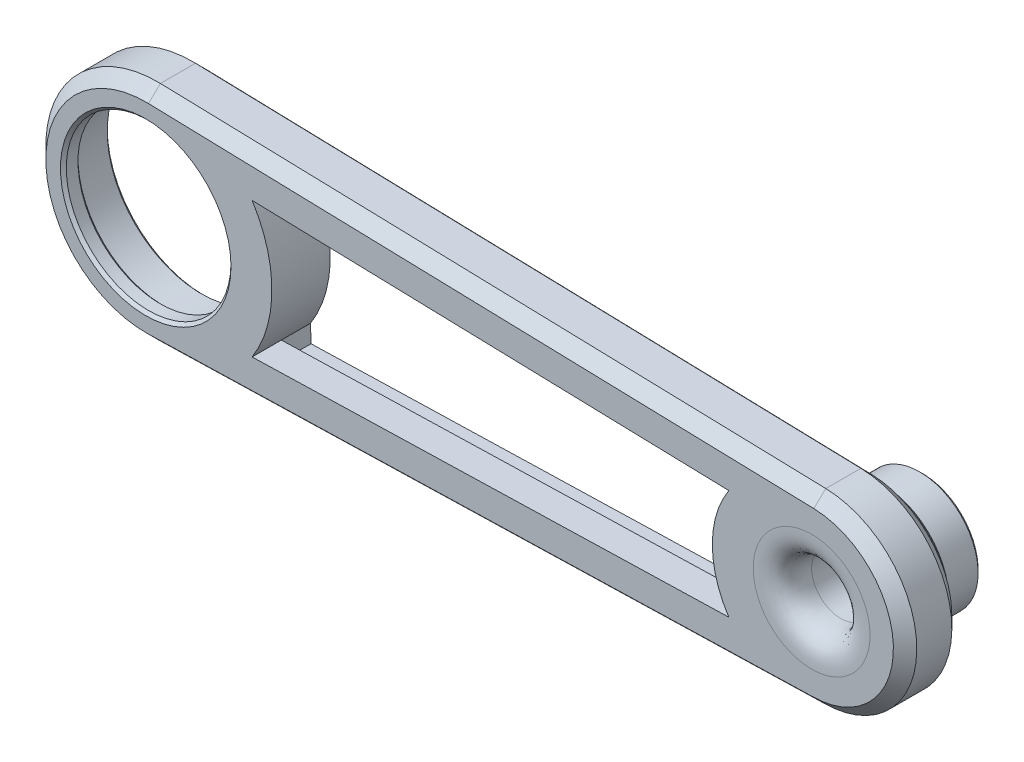
SolidWorks part; units mm, degrees
material "PEI"
ref_plane "前视基准面" through (0, 0, 0) normal (0, 0, 1) x (1, 0, 0)
ref_plane "上视基准面" through (0, 0, 0) normal (0, 1, 0) x (1, 0, 0)
ref_plane "右视基准面" through (0, 0, 0) normal (1, 0, 0) x (0, 0, -1)
other "Configuration Table"
sketch "草图1" plane through (0, 0, 0) normal (0, 0, 1) x (1, 0, 0)
  line L0 (0, 0) -> (114, 0) construction
  line L1 (0.5194, 19.0929) -> (114.4351, 15.9941)
  line L2 (0.5204, -19.0929) -> (114, -16)
  circle A0 centre (114, 0) radius 16
  circle A1 centre (0, 0) radius 16.1
  circle A2 centre (0, 0) radius 19.1
  dimension "D1" = 32.2
  dimension "D3" = 32
  dimension "D2" = 3
  dimension "D4" = 114
extrude "凸台-拉伸1" add sketch "草图1" along normal blind 10
sketch "草图2" plane through (0, 0, 10) normal (0, 0, 1) x (1, 0, 0)
  circle A0 centre (0, 0) radius 16.1 construction
  circle A1 centre (0, 0) radius 16.1
  circle A2 centre (0, 0) radius 14.1
  dimension "D1" = 2
extrude "凸台-拉伸2" add sketch "草图2" against normal blind 3
sketch "草图3" plane through (0, 0, 0) normal (0, 0, -1) x (-1, 0, 0)
  arc A0 (-114.4351, 15.9941) -> (-114, -16) centre (-114, 0) ccw construction
  arc A1 (-114.4351, 15.9941) -> (-114, -16) centre (-114, 0) ccw
  circle A2 centre (-114, 0) radius 10
  dimension "D1" = 20
extrude "凸台-拉伸3" add sketch "草图3" along normal blind 9 contours A2
sketch "草图4" plane through (0, 0, 0) normal (0, 0, -1) x (-1, 0, 0)
  circle A0 centre (-114, 0) radius 10 construction
  circle A1 centre (-114, 0) radius 10
  circle A2 centre (-114, 0) radius 12
  dimension "D1" = 2
extrude "凸台-拉伸4" add sketch "草图4" along normal blind 2
chamfer "倒角1" distance 0.5 angle 45 5 edges at (14.1, 0, 10) (16.1, 0, 0) (14.1, 0, 7) (102, 0, -2) (104, 0, -9)
chamfer "倒角2" distance 2 angle 45 8 edges at (129.9985, -0.2176, 10) (57.4772, 17.5435, 10) (-19.1, -0.0005, 10) (57.2602, -17.5465, 10) (129.9985, -0.2176, 0) (57.4772, 17.5435, 0) (-19.1, -0.0005, 0) (57.2602, -17.5465, 0)
sketch "草图5" plane through (0, 0, 0) normal (0, 0, -1) x (-1, 0, 0)
  line L0 (-0.329, 12.0955) -> (-114.2447, 8.9967)
  line L1 (-113.9182, -8.9996) -> (-0.3297, -12.0955)
  line L2 (-0.465, 17.0937) -> (-114.3807, 13.9948)
  line L3 (-113.9737, -14) -> (-0.4659, -17.0937)
  line L4 (-0.465, 17.0937) -> (-114.3807, 13.9948)
  line L5 (-113.9737, -14) -> (-0.4659, -17.0937)
  arc A0 (-114.2447, 8.9967) -> (-113.9182, -8.9996) centre (-114, 0) ccw
  arc A1 (-0.3297, -12.0955) -> (-0.329, 12.0955) centre (0, 0) ccw
  arc A2 (-114.3807, 13.9948) -> (-113.9737, -14) centre (-114, 0) ccw
  arc A3 (-0.4659, -17.0937) -> (-0.465, 17.0937) centre (0, 0) ccw
  arc A4 (-114.3807, 13.9948) -> (-113.9737, -14) centre (-114, 0) ccw
  arc A5 (-0.4659, -17.0937) -> (-0.465, 17.0937) centre (0, 0) ccw
  circle A6 centre (-114, 0) radius 12 construction
  circle A7 centre (0, 0) radius 16.6 construction
  circle A30 centre (0, 0) radius 16.6
  circle A31 centre (-114, 0) radius 12
  circle A32 centre (-114, 0) radius 17
  circle A33 centre (0, 0) radius 21.6
  dimension "D1" = 0
  dimension "D2" = 5
  dimension "D3" = 5
extrude "切除-拉伸1" cut sketch "草图5" against normal up to surface (10 mm away) contours A33 L0 A32 L1 up to face at (56.3853, -0.0516, 10)
sketch "草图6" plane through (0, 0, 0) normal (0, 0, -1) x (-1, 0, 0)
  line L0 (-99.8245, -9.3838) -> (-18.2158, -11.608) construction
  line L1 (-18.2152, 11.609) -> (-99.8279, 9.3889) construction
  line L2 (-99.8245, -9.3838) -> (-18.2158, -11.608)
  line L3 (-18.2152, 11.609) -> (-99.8279, 9.3889)
  line L4 (-18.2967, 14.6079) -> (-99.9094, 12.3877)
  line L5 (-99.9062, -12.3826) -> (-18.2975, -14.6069)
  line L6 (-99.9094, 12.3877) -> (-99.8279, 9.3889)
  line L7 (-99.8245, -9.3838) -> (-99.9062, -12.3826)
  line L8 (-18.2967, 14.6079) -> (-18.2152, 11.609)
  line L9 (-18.2158, -11.608) -> (-18.2975, -14.6069)
  dimension "D1" = 3
extrude "切除-拉伸2" cut sketch "草图6" against normal blind 5
sketch "草图7" plane through (0, 0, -9) normal (0, 0, -1) x (-1, 0, 0)
  circle A0 centre (-114, 0) radius 5
  dimension "D1" = 10
extrude "切除-拉伸3" cut sketch "草图7" against normal up to surface (19 mm away) up to face at (59.1604, 0.0017, 10)
fillet "圆角1" radius 5 1 edges at (119, 0, 10)
equation "\"D4@草图1\"= \"连接杆_前_长度\""
equation "\"连接杆_前_长度\"= 114"
